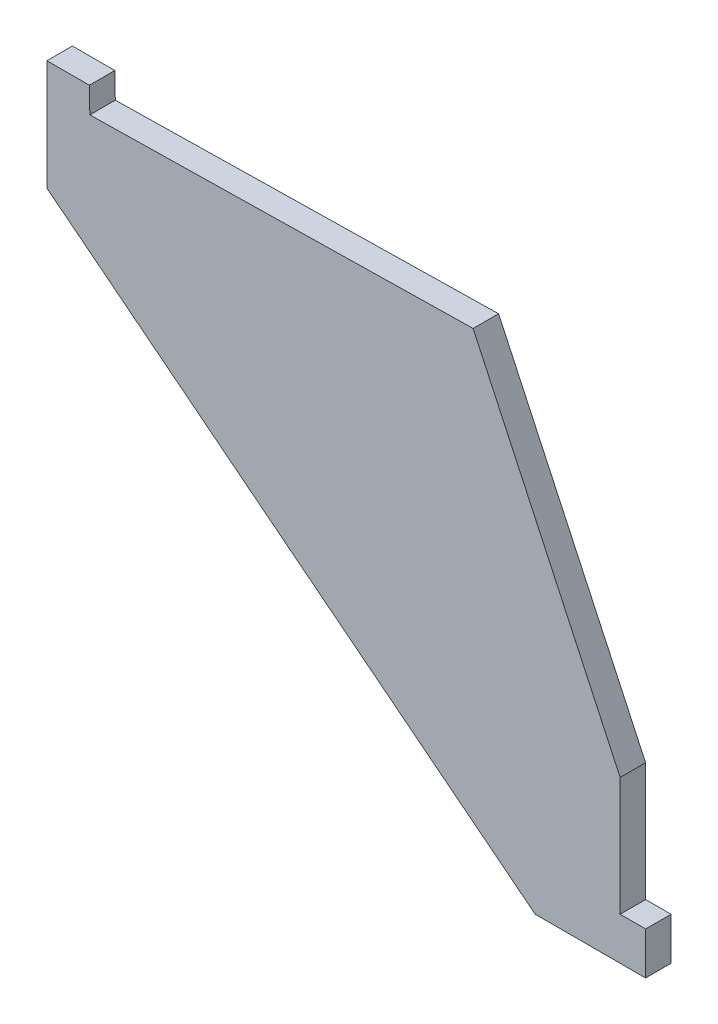
SolidWorks part; units mm, degrees
ref_plane "Plan de face" through (0, 0, 0) normal (0, 0, 1) x (1, 0, 0)
ref_plane "Plan de dessus" through (0, 0, 0) normal (0, 1, 0) x (1, 0, 0)
ref_plane "Plan de droite" through (0, 0, 0) normal (1, 0, 0) x (0, 0, -1)
sketch "Esquisse1" plane through (0, 0, 0) normal (0, 0, 1) x (1, 0, 0)
  line L0 (-75.997, 82.3714) -> (-75.997, 76.3732)
  line L1 (-75.997, 82.3714) -> (-65.997, 82.3714)
  line L2 (-65.997, 82.3714) -> (-65.8923, 76.3732)
  line L3 (65.003, -34.2186) -> (59.003, -34.2186)
  line L4 (-65.8923, 76.3732) -> (24.3762, 77.9488)
  line L5 (24.3762, 77.9488) -> (59.003, 3.6914)
  line L7 (65.003, -34.2186) -> (65.003, -24.2186)
  line L8 (65.003, -24.2186) -> (59.003, -24.2186)
  line L9 (59.003, -34.2186) -> (39.003, -34.2186)
  line L10 (59.003, 3.6914) -> (59.003, -24.2186)
  line L13 (39.003, -34.2186) -> (-75.997, 56.3732)
  line L14 (-75.997, 56.3732) -> (-75.997, 76.3732)
  dimension "D2" = 141
  dimension "D3" = 10
  dimension "D4" = 5.9982
  dimension "D5" = 6
  dimension "D6" = 10
  dimension "D7" = 27.91
  dimension "D8" = 155
  dimension "D9" = 114
  dimension "D10" = 6
  dimension "D11" = 116.59
  dimension "D12" = 20
  dimension "D13" = 5.9982
  dimension "D14" = 20
extrude "Boss.-Extru.2" add sketch "Esquisse1" along normal blind 6
